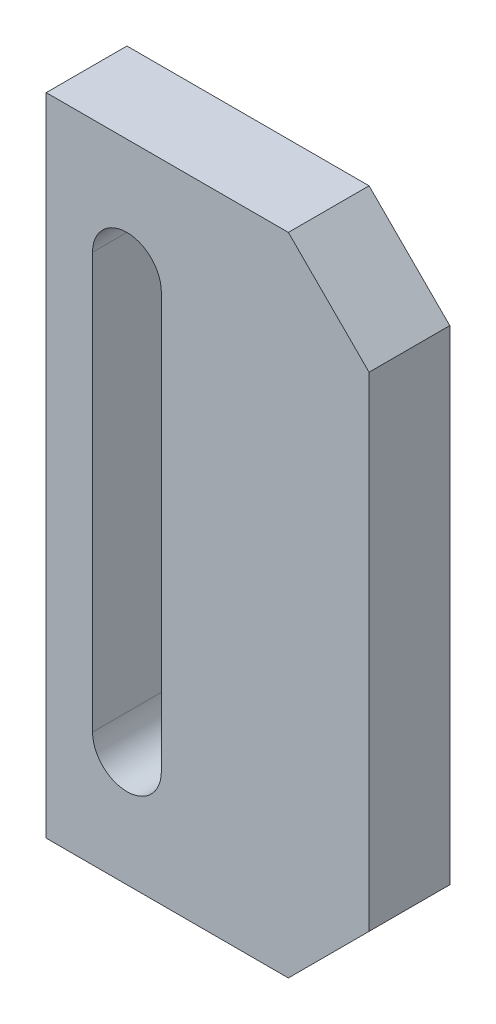
SolidWorks part; units mm, degrees
material "PET"
ref_plane "Front Plane" through (0, 0, 0) normal (0, 0, 1) x (1, 0, 0)
ref_plane "Top Plane" through (0, 0, 0) normal (0, 1, 0) x (1, 0, 0)
ref_plane "Right Plane" through (0, 0, 0) normal (1, 0, 0) x (0, 0, -1)
sketch "Sketch1" plane through (0, 0, 0) normal (0, 0, 1) x (1, 0, 0)
  line L1 (112.7975, -2418.983) -> (125.4975, -2418.983)
  line L2 (112.7975, -2418.983) -> (112.7975, -2393.583)
  line L3 (112.7975, -2393.583) -> (125.4975, -2393.583)
  line L4 (125.4975, -2418.983) -> (125.4975, -2393.583)
  point P5 (112.7975, -2393.583)
  dimension "D1" = 12.7
extrude "Boss-Extrude1" add sketch "Sketch1" along normal blind 3.175
chamfer "Chamfer1" distance 3.175 angle 45 2 edges at (125.4975, -2418.983, 1.5875) (125.4975, -2393.583, 1.5875)
hole_wizard "#2 Clearance Slot1" positions "Sketch2" profile "Sketch3" size "#2" standard "ANSI Inch" slot yes
sketch "Sketch2" plane through (0, 0, 3.175) normal (0, 0, 1) x (1, 0, 0)
  line L0 (115.9725, -2415.808) -> (115.9725, -2396.758) construction
  line L1 (112.7975, -2393.583) -> (112.7975, -2418.983) construction
  point P0 (115.9725, -2406.283)
  point P5 (115.7456, -2406.283)
  point P8 (112.7975, -2406.283)
  dimension "D1" = 19.05
  dimension "D2" = 3.175
sketch "Sketch3" plane through (115.9725, -2406.283, 3.175) normal (1, 0, 0) x (0, -1, 0)
  line L0 (0, 0) -> (0, 7.1627)
  line L1 (0, 7.1627) -> (1.3525, 6.35)
  line L2 (1.3525, 6.35) -> (1.3525, 0)
  line L5 (1.3525, 0) -> (0, 0)
  line L10 (0, 7.1627) -> (-1.3526, 6.35) construction
  line L11 (0, -6.35) -> (0, 107.95) construction
  dimension "Hole Dia." = 2.7051
  dimension "Hole Depth" = 6.35
  dimension "Drill Angle" = 118
